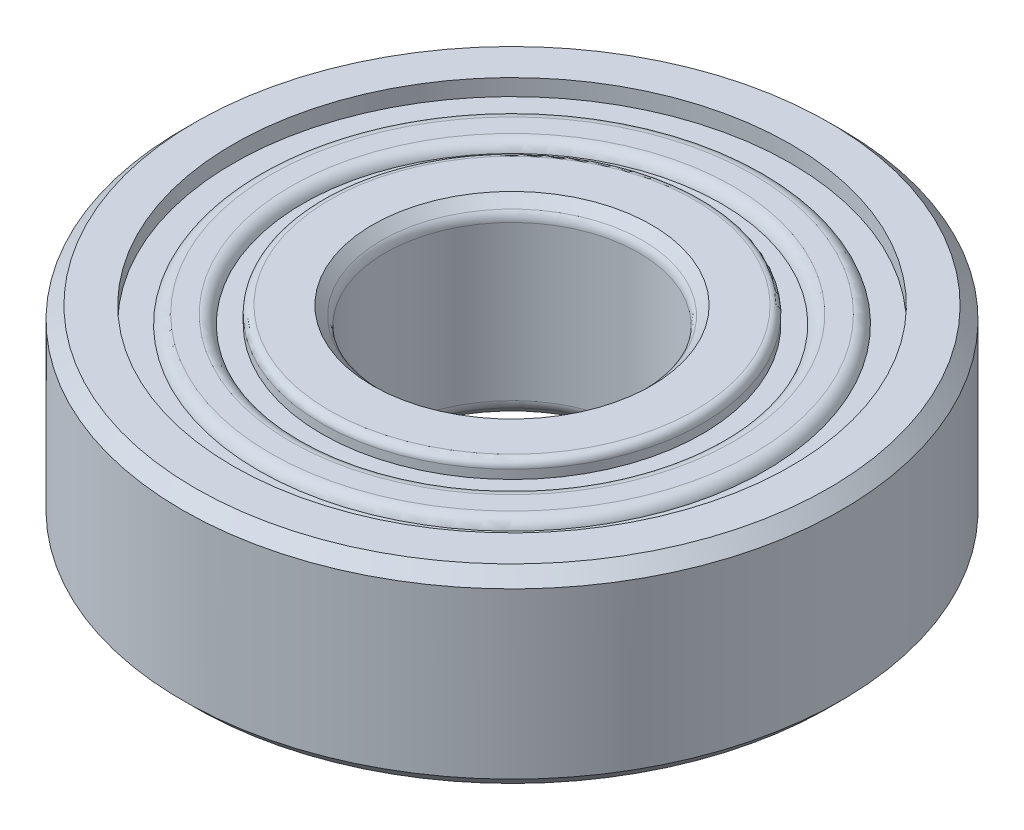
SolidWorks part; units mm, degrees
ref_plane "Front Plane" through (0, 0, 0) normal (0, 0, 1) x (1, 0, 0)
ref_plane "Top Plane" through (0, 0, 0) normal (0, 1, 0) x (1, 0, 0)
ref_plane "Right Plane" through (0, 0, 0) normal (1, 0, 0) x (0, 0, -1)
sketch "Sketch1" plane through (0, 0, 0) normal (0, 1, 0) x (1, 0, 0)
  circle A0 centre (0, 0) radius 26
  dimension "D1" = 52
extrude "Boss-Extrude1" add sketch "Sketch1" along normal blind 7.5
sketch "Sketch2" plane through (0, 7.5, 0) normal (0, 1, 0) x (1, 0, 0)
  circle A0 centre (0, 0) radius 22
  dimension "D1" = 44
extrude "Cut-Extrude1" cut sketch "Sketch2" against normal blind 1.3
sketch "Sketch3" plane through (0, 6.2, 0) normal (0, 1, 0) x (1, 0, 0)
  circle A0 centre (0, 0) radius 20
  circle A1 centre (0, 0) radius 16.5
  dimension "D1" = 40
  dimension "D2" = 33
extrude "Boss-Extrude2" add sketch "Sketch3" along normal blind 0.7
sketch "Sketch4" plane through (0, 6.2, 0) normal (0, 1, 0) x (1, 0, 0)
  circle A0 centre (0, 0) radius 15
  circle A1 centre (0, 0) radius 10
  dimension "D1" = 30
  dimension "D2" = 20
extrude "Boss-Extrude3" add sketch "Sketch4" along normal blind 1.3
sketch "Sketch5" plane through (0, 6.2, 0) normal (0, 1, 0) x (1, 0, 0)
  circle A1 centre (0, 0) radius 10
  circle A2 centre (0, 0) radius 10
  dimension "D1" = 0
extrude "Cut-Extrude2" cut sketch "Sketch5" against normal through all
chamfer "Chamfer1" distance 1 angle 45 1 edges at (0, 7.5, 26)
chamfer "Chamfer2" distance 1 angle 45 1 edges at (0, 7.5, 10)
fillet "Fillet1" radius 1 2 edges at (0, 6.9, 16.5) (0, 6.9, 20)
fillet "Fillet2" radius 1 1 edges at (0, 6.5, 10)
fillet "Fillet3" radius 0.6 1 edges at (0, 7.5, 15)
mirror "Mirror2" of "Fillet3", "Fillet2", "Fillet1", "Chamfer2", "Chamfer1", "Cut-Extrude2", "Boss-Extrude3", "Cut-Extrude1", "Boss-Extrude2", "Boss-Extrude1"
equation "\"0.5.00mm\"=10"
